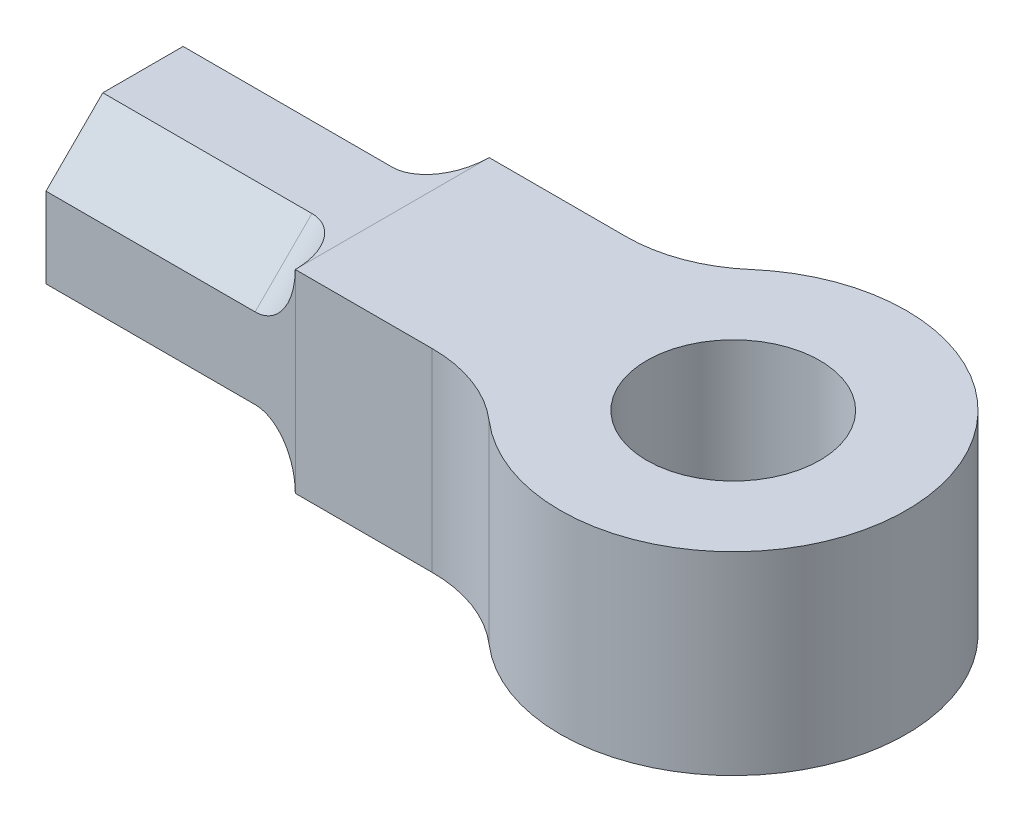
SolidWorks part; units mm, degrees
ref_plane "Front Plane" through (0, 0, 0) normal (0, 0, 1) x (1, 0, 0)
ref_plane "Top Plane" through (0, 0, 0) normal (0, 1, 0) x (1, 0, 0)
ref_plane "Right Plane" through (0, 0, 0) normal (1, 0, 0) x (0, 0, -1)
sketch "Croquis1" plane through (0, 0, 0) normal (0, 1, 0) x (1, 0, 0)
  line L1 (-20.7123, 14) -> (-49.2574, 14)
  line L3 (-20.7123, -14) -> (-49.2574, -14)
  line L4 (-49.2574, 14) -> (-49.2574, -14)
  arc A0 (-20.7123, -14) -> (-20.7123, 14) centre (0, 0) ccw
  circle A1 centre (0, 0) radius 12.5
  dimension "D1" = 50
  dimension "D2" = 25
  dimension "D3" = 14
extrude "Saliente-Extruir1" add sketch "Croquis1" along normal mid plane 28
sketch "Croquis2" plane through (-49.2574, 0, 0) normal (-1, 0, 0) x (0, 0, 1)
  line L0 (-14, 14) -> (14, 14) construction
  line L1 (5.8001, 14.0026) -> (-5.8001, 14.0026)
  line L2 (-5.8001, 14.0026) -> (-14.0026, 5.8001)
  line L3 (-14.0026, 5.8001) -> (-14.0026, -5.8001)
  line L4 (-14.0026, -5.8001) -> (-5.8001, -14.0026)
  line L5 (-5.8001, -14.0026) -> (5.8001, -14.0026)
  line L6 (5.8001, -14.0026) -> (14.0026, -5.8001)
  line L7 (14.0026, -5.8001) -> (14.0026, 5.8001)
  line L8 (14.0026, 5.8001) -> (5.8001, 14.0026)
  circle A0 centre (0, 0) radius 14.0026 construction
extrude "Saliente-Extruir2" add sketch "Croquis2" along normal blind 36
fillet "Redondeo1" radius 5.8 4 edges
fillet "Redondeo2" radius 20 2 edges at (-20.7123, 0, -14) (-20.7123, 0, 14)
